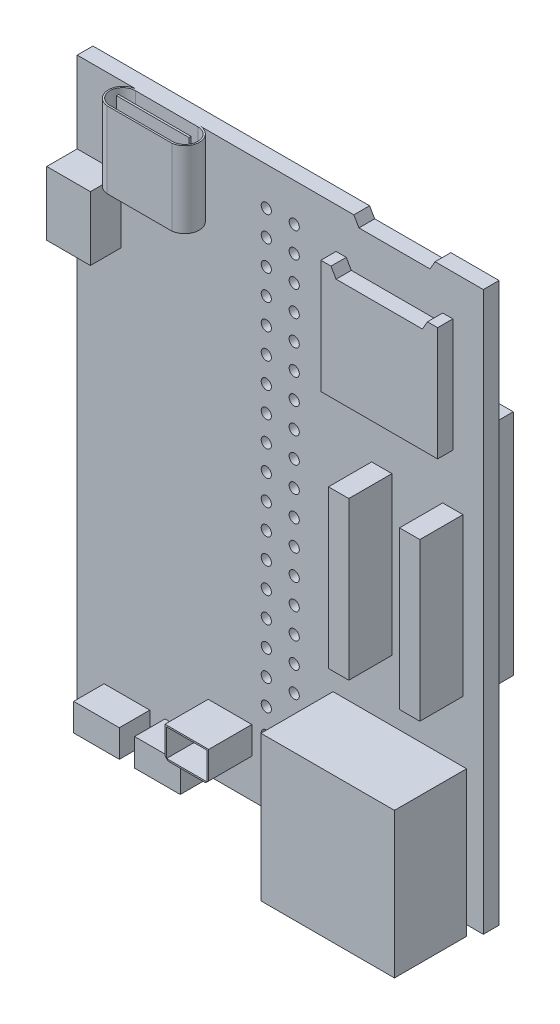
SolidWorks part; units mm, degrees
ref_plane "Front Plane" through (0, 0, 0) normal (1, 0, 0) x (0, 1, 0)
ref_plane "Top Plane" through (0, 0, 0) normal (0, 0, 1) x (0, 1, 0)
ref_plane "Right Plane" through (0, 0, 0) normal (0, 1, 0) x (-1, 0, 0)
sketch "Sketch1" plane through (0, 0, 0) normal (0, 0, 1) x (0, 1, 0)
  line L1 (-27.5, -20) -> (27.5, -20)
  line L2 (-27.5, -20) -> (-27.5, 20)
  line L3 (-27.5, 20) -> (27.5, 20)
  line L4 (27.5, -20) -> (27.5, 20)
  line L5 (-27.5, -20) -> (27.5, 20) construction
  line L6 (-27.5, 20) -> (27.5, -20) construction
  point P0 (0, 0)
  dimension "D1" = 55
  dimension "D2" = 40
extrude "Boss-Extrude1" add sketch "Sketch1" along normal blind 1.55
sketch "Sketch2" plane through (0, 0, 1.55) normal (0, 0, 1) x (1, 0, 0)
  line L0 (20, -27.5) -> (20, 27.5) construction
  line L1 (5.2, -14.2) -> (18.35, -14.2)
  line L2 (5.2, -14.2) -> (5.2, -28.5)
  line L3 (5.2, -28.5) -> (18.35, -28.5)
  line L4 (18.35, -14.2) -> (18.35, -28.5)
  line L5 (5.2, -14.2) -> (18.35, -28.5) construction
  line L6 (5.2, -28.5) -> (18.35, -14.2) construction
  line L7 (-20, -27.5) -> (20, -27.5) construction
  point P0 (11.775, -21.35)
  dimension "D1" = 1.65
  dimension "D2" = 1
  dimension "D3" = 14.3
  dimension "D4" = 13.15
extrude "Boss-Extrude2" add sketch "Sketch2" along normal blind 7.1
sketch "Sketch3" plane through (0, -28.5, 0) normal (0, -1, 0) x (1, 0, 0)
  line L0 (5.2, 8.65) -> (18.35, 8.65) construction
  line L1 (5.525, 1.85) -> (18.025, 1.85)
  line L2 (5.525, 1.85) -> (5.525, 8.35)
  line L3 (5.525, 8.35) -> (18.025, 8.35)
  line L4 (18.025, 1.85) -> (18.025, 8.35)
  line L5 (5.525, 1.85) -> (18.025, 8.35) construction
  line L6 (5.525, 8.35) -> (18.025, 1.85) construction
  line L7 (5.2, 8.65) -> (18.35, 8.65)
  line L8 (18.35, 8.65) -> (18.35, 1.55) construction
  line L9 (18.35, 8.65) -> (18.35, 1.55)
  line L10 (11.775, 8.65) -> (11.775, 2.4652) construction
  line L11 (18.35, 5.1) -> (11.2496, 5.1) construction
  line L13 (6.225, 6.85) -> (19.3448, 6.85)
  line L14 (6.225, 6.85) -> (6.225, 5.3523)
  line L15 (6.225, 5.3523) -> (19.3448, 5.3523)
  line L16 (19.3448, 6.85) -> (19.3448, 5.3523)
  line L17 (5.525, 6.1356) -> (5.2, 6.1356) construction
  line L18 (5.2, 8.65) -> (5.2, 1.55) construction
  line L19 (18.025, 6.1356) -> (18.35, 6.1356) construction
  point P0 (11.775, 5.1)
  point P12 (11.775, 5.1)
  dimension "D1" = 12.5
  dimension "D2" = 6.5
  dimension "D3" = 1.5
  dimension "D5" = 0.7
  dimension "D6" = 1.4977
extrude "Cut-Extrude1" cut sketch "Sketch3" against normal offset from surface (13.3 mm away) 1 contours L1 L4 L3 L2 L13 L16 L15 L14 region at (11.6777, -28.5, 4.8217) up to face at (11.775, -14.2, 5.1)
sketch "Sketch4" plane through (0, 0, 1.55) normal (0, 0, 1) x (1, 0, 0)
  line L0 (20, 27.5) -> (-20, 27.5) construction
  line L1 (-15.5, 27.5) -> (-6.55, 27.5)
  line L2 (-15.5, 27.5) -> (-15.5, 20)
  line L3 (-15.5, 20) -> (-6.55, 20)
  line L4 (-6.55, 27.5) -> (-6.55, 20)
  line L5 (-20, 27.5) -> (-20, -27.5) construction
  dimension "D1" = 4.5
  dimension "D2" = 7.5
  dimension "D3" = 8.95
extrude "Boss-Extrude3" add sketch "Sketch4" along normal blind 2.85
sketch "Sketch5" plane through (0, 27.5, 0) normal (0, 1, 0) x (-1, 0, 0)
  line L0 (6.55, 4.4) -> (15.5, 4.4) construction
  line L1 (6.55, 4.4) -> (15.5, 4.4) construction
  line L2 (6.55, 1.55) -> (15.5, 1.55) construction
  line L4 (11.025, 4.4) -> (11.025, 1.9427) construction
  line L7 (7.8105, 1.55) -> (6.55, 1.55)
  line L8 (6.55, 1.55) -> (6.55, 4.4)
  line L9 (6.55, 4.4) -> (7.8105, 4.4)
  line L10 (6.55, 4.4) -> (7.8105, 4.4)
  line L11 (14.2395, 4.4) -> (15.5, 4.4)
  line L12 (15.5, 4.4) -> (15.5, 2.975)
  line L13 (15.5, 2.975) -> (15.5, 1.55)
  line L14 (15.5, 1.55) -> (14.2395, 1.55)
  line L15 (7.95, 2.975) -> (14.1, 2.975) construction
  line L16 (7.95, 4.2305) -> (14.1, 4.2305)
  line L17 (7.95, 1.7195) -> (14.1, 1.7195)
  line L19 (7.45, 2.875) -> (14.6, 2.875)
  line L20 (7.45, 2.875) -> (7.45, 3.075)
  line L21 (7.45, 3.075) -> (14.6, 3.075)
  line L22 (14.6, 2.875) -> (14.6, 3.075)
  line L23 (7.45, 2.875) -> (14.6, 3.075) construction
  line L24 (7.45, 3.075) -> (14.6, 2.875) construction
  arc A0 (7.8105, 1.55) -> (7.8105, 4.4) centre (7.9857, 2.975) cw
  arc A1 (14.2395, 1.55) -> (14.2395, 4.4) centre (14.0643, 2.975) ccw
  arc A2 (7.95, 4.2305) -> (7.95, 1.7195) centre (7.95, 2.975) ccw
  arc A3 (14.1, 1.7195) -> (14.1, 4.2305) centre (14.1, 2.975) ccw
  point P17 (11.025, 2.975)
  point P22 (11.025, 2.975)
  line M7 (15.5, 1.55) -> (15.5, 4.4)
  line M8 (15.5, 4.4) -> (6.55, 4.4)
  line M9 (6.55, 4.4) -> (6.55, 1.55)
  dimension "D1" = 1.4357
  dimension "D2" = 6.15
  dimension "D3" = 1.2555
  dimension "D4" = 7.15
  dimension "D5" = 0.2
extrude "Cut-Extrude2" cut sketch "Sketch5" against normal up to surface (7.5 mm away) contours A0 M9 M8 | L7 A0 L8 | A1 L14 M7 | A1 M7 M8 region at (-15.1905, 27.5, 1.8704) region at (-15.1905, 27.5, 4.0796) region at (-6.8595, 27.5, 4.0796) region at (-6.8595, 27.5, 1.8704) up to face at (-11.025, 20, 2.975)
extrude "Cut-Extrude3" cut sketch "Sketch5<3>" against normal offset from surface (7 mm away) 0.5 contours L17 A3 L16 A2 L22 L19 L20 L21 region at (-11.025, 27.5, 4.1404) up to face at (-11.025, 20, 2.975)
sketch "Sketch5<3>" plane through (0, 27.5, 0) normal (0, 1, 0) x (-1, 0, 0) same geometry as "Sketch5"
sketch "Sketch6" plane through (0, 0, 1.55) normal (0, 0, 1) x (1, 0, 0)
  line L0 (16, 23.5) -> (15.5, 22.634)
  line L1 (17, 12.3) -> (5.5, 12.3)
  line L2 (17, 12.3) -> (17, 23.5)
  line L3 (17, 23.5) -> (16, 23.5)
  line L4 (5.5, 12.3) -> (5.5, 23.5)
  line L5 (18.35, -28.5) -> (18.35, -14.2) construction
  line L6 (18.35, -28.5) -> (18.35, -14.2) construction
  line L7 (15.5, 22.634) -> (7, 22.634)
  line L8 (7, 22.634) -> (6.5, 23.5)
  line L9 (6.5, 23.5) -> (5.5, 23.5)
  line L10 (20, 27.5) -> (-7.8105, 27.5) construction
  line L12 (20, -27.5) -> (20, 27.5) construction
  dimension "D1" = 120
  dimension "D2" = 8.5
  dimension "D3" = 3
  dimension "D4" = 1
  dimension "D5" = 11.5
  dimension "D6" = 11.2
  dimension "D7" = 4
extrude "Boss-Extrude4" add sketch "Sketch6" along normal blind 1.5
sketch "Sketch7" plane through (0, 0, 1.55) normal (0, 0, 1) x (1, 0, 0)
  line L3 (16, 23.5) -> (15.5, 22.634) construction
  line L5 (7, 22.634) -> (6.5, 23.5) construction
  line L6 (15.5, 22.634) -> (7, 22.634) construction
  line L7 (16, 23.5) -> (15.5, 22.634) construction
  line L8 (7, 22.634) -> (6.5, 23.5) construction
  line L9 (15.5, 22.634) -> (7, 22.634) construction
  line L10 (7.25, 27.5) -> (7.75, 26.634)
  line L11 (20, 27.5) -> (-7.8105, 27.5) construction
  line L12 (15.25, 27.5) -> (14.75, 26.634)
  line L13 (7.75, 26.634) -> (14.75, 26.634)
  line L14 (7.25, 27.5) -> (15.25, 27.5)
  point P10 (11.25, 26.634)
  point P11 (11.25, 22.634)
  dimension "D1" = 7
  dimension "D2" = 120
extrude "Cut-Extrude4" cut sketch "Sketch7" against normal blind 10
sketch "Sketch8" plane through (0, 0, 1.55) normal (0, 0, 1) x (1, 0, 0)
  line L0 (-20, -27.5) -> (5.2, -27.5) construction
  line L1 (-17.35, -27.5) -> (-12.85, -27.5)
  line L2 (-17.35, -27.5) -> (-17.35, -24.8)
  line L3 (-17.35, -24.8) -> (-12.85, -24.8)
  line L4 (-12.85, -27.5) -> (-12.85, -24.8)
  line L5 (-20, 27.5) -> (-20, -27.5) construction
  line L6 (-12.1, -27.5) -> (-12.1, -22.0575) construction
  line L7 (-6.85, -24.8) -> (-11.35, -24.8)
  line L8 (-11.35, -27.5) -> (-11.35, -24.8)
  line L9 (-6.85, -27.5) -> (-11.35, -27.5)
  line L10 (-6.85, -27.5) -> (-6.85, -24.8)
  line L12 (-7.1, -21) -> (-2.8, -21)
  line L13 (-7.1, -21) -> (-7.1, -24)
  line L14 (-7.1, -24) -> (-2.8, -24)
  line L15 (-2.8, -21) -> (-2.8, -24)
  line M20 (-20, -27.5) -> (5.2, -27.5)
  dimension "D1" = 4.5
  dimension "D2" = 2.7
  dimension "D3" = 13.15
  dimension "D4" = 1.5
  dimension "D5" = 12.9
  dimension "D6" = 3.5
  dimension "D7" = 3
  dimension "D8" = 4.3
extrude "Boss-Extrude5" add sketch "Sketch8" along normal blind 3 contours L10 L7 L8 M20 | L4 L3 L2 M20 region at (-15.1, -26.15, 1.55) region at (-9.1, -26.15, 1.55)
sketch "Sketch9" plane through (0, -27.5, 0) normal (0, -1, 0) x (1, 0, 0)
  line L0 (-12.1, 3.8788) -> (-12.1, 2.2212) construction
  line L1 (-11.35, 4.55) -> (-11.35, 1.55) construction
  line L2 (-12.85, 4.55) -> (-12.85, 1.55) construction
  line L3 (-17.35, 4.55) -> (-17.35, 1.55) construction
  line L5 (-12.1, 3.05) -> (-12.85, 3.05) construction
  line L6 (-11.35, 4.55) -> (-11.35, 1.55) construction
  line L7 (-12.85, 4.55) -> (-12.85, 1.55) construction
  line L8 (-17.35, 4.55) -> (-17.35, 1.55) construction
  line L9 (-17.35, 4.55) -> (-12.85, 4.55) construction
  line L10 (-12.1, 3.05) -> (-11.35, 3.05) construction
  line L11 (-17.35, 4.55) -> (-12.85, 4.55) construction
  line L13 (-15.1, 4.55) -> (-15.1, 1.55) construction
  circle A0 centre (-15.1, 3.05) radius 1
  circle A1 centre (-9.1, 3.05) radius 1
  point P10 (-12.85, 3.05)
  point P18 (-17.1, 4.55)
  point P21 (0, 0)
  point P22 (0, 0)
  dimension "D1" = 2
extrude "Boss-Extrude6" add sketch "Sketch9" along normal blind 0.5 contours A1 | A0 region at (-9.1, -27.5, 3.05)
sketch "Sketch10" plane through (0, 0, 1.55) normal (0, 0, 1) x (1, 0, 0)
  line L0 (17, 12.3) -> (17, 23.5) construction
  line L1 (17, 12.3) -> (17, 23.5) construction
  line L2 (18.35, -14.2) -> (5.2, -14.2) construction
  line L3 (18, 7.3) -> (16, 7.3)
  line L4 (18, 7.3) -> (18, -8.2)
  line L5 (18, -8.2) -> (16, -8.2)
  line L6 (16, 7.3) -> (16, -8.2)
  line L8 (13.5, 8.7091) -> (13.5, -10.2301) construction
  line L9 (9, -8.2) -> (11, -8.2)
  line L10 (11, 7.3) -> (11, -8.2)
  line L11 (9, 7.3) -> (11, 7.3)
  line L12 (9, 7.3) -> (9, -8.2)
  line L13 (20, -27.5) -> (20, 27.5) construction
  dimension "D1" = 15.5
  dimension "D2" = 2
  dimension "D3" = 6
  dimension "D4" = 5
  dimension "D5" = 2
extrude "Boss-Extrude7" add sketch "Sketch10" along normal blind 4.25
extrude "Boss-Extrude9" add sketch "Sketch8<4>" along normal blind 4.25 separate body contours L15 L12 L13 L14 region at (-4.95, -22.5, 1.55)
sketch "Sketch8<4>" plane through (0, 0, 1.55) normal (0, 0, 1) x (1, 0, 0) same geometry as "Sketch8"
shell "Shell2" thickness 0.15 removed face at (-4.95, -22.5, 5.8)
combine bodies "Combine1" operation type add bodies to combine 111 113
chamfer "Chamfer1" distance 0.3 angle 45 2 edges at (-7.1, -24, 3.675) (-2.8, -24, 3.675) tangent propagation no
sketch "Sketch11" plane through (0, 0, 1.55) normal (0, 0, 1) x (1, 0, 0)
  line L0 (7.25, 27.5) -> (-7.8105, 27.5) construction
  line L1 (2.75, -25.5) -> (-2.75, -25.5) construction
  line L2 (2.75, -25.5) -> (2.75, 25.5) construction
  line L3 (2.75, 25.5) -> (-2.75, 25.5) construction
  line L4 (-2.75, -25.5) -> (-2.75, 25.5) construction
  line L5 (-6.85, -27.5) -> (5.2, -27.5) construction
  line L6 (-14.2395, 27.5) -> (-20, 27.5) construction
  line L10 (2.75, 0) -> (20, 0) construction
  line L11 (20, -27.5) -> (20, 27.5) construction
  line L12 (-2.75, 0) -> (-20, 0) construction
  line L13 (-20, 27.5) -> (-20, -27.5) construction
  line L16 (0, 25.5) -> (0, -25.5) construction
  line L17 (0, 23.75) -> (1.375, 23.75) construction
  line L18 (1.375, 23.75) -> (2.75, 23.75) construction
  line L19 (1.375, 23.75) -> (1.375, 25.5) construction
  line L20 (1.375, -23.75) -> (1.375, -25.5) construction
  circle A0 centre (1.375, 23.75) radius 0.5
  circle A1 centre (1.375, 21.25) radius 0.5
  circle A2 centre (1.375, 18.75) radius 0.5
  circle A3 centre (1.375, 16.25) radius 0.5
  circle A4 centre (1.375, 13.75) radius 0.5
  circle A5 centre (1.375, 11.25) radius 0.5
  circle A6 centre (1.375, 8.75) radius 0.5
  circle A7 centre (1.375, 6.25) radius 0.5
  circle A8 centre (1.375, 3.75) radius 0.5
  circle A9 centre (1.375, 1.25) radius 0.5
  circle A10 centre (1.375, -1.25) radius 0.5
  circle A11 centre (1.375, -3.75) radius 0.5
  circle A12 centre (1.375, -6.25) radius 0.5
  circle A13 centre (1.375, -8.75) radius 0.5
  circle A14 centre (1.375, -11.25) radius 0.5
  circle A15 centre (1.375, -13.75) radius 0.5
  circle A16 centre (1.375, -16.25) radius 0.5
  circle A17 centre (1.375, -18.75) radius 0.5
  circle A18 centre (1.375, -21.25) radius 0.5
  circle A19 centre (1.375, -23.75) radius 0.5
  circle A20 centre (-1.375, -23.75) radius 0.5
  circle A21 centre (-1.375, -21.25) radius 0.5
  circle A22 centre (-1.375, -18.75) radius 0.5
  circle A23 centre (-1.375, -16.25) radius 0.5
  circle A24 centre (-1.375, -13.75) radius 0.5
  circle A25 centre (-1.375, -11.25) radius 0.5
  circle A26 centre (-1.375, -8.75) radius 0.5
  circle A27 centre (-1.375, -6.25) radius 0.5
  circle A28 centre (-1.375, -3.75) radius 0.5
  circle A29 centre (-1.375, -1.25) radius 0.5
  circle A30 centre (-1.375, 1.25) radius 0.5
  circle A31 centre (-1.375, 3.75) radius 0.5
  circle A32 centre (-1.375, 6.25) radius 0.5
  circle A33 centre (-1.375, 8.75) radius 0.5
  circle A34 centre (-1.375, 11.25) radius 0.5
  circle A35 centre (-1.375, 13.75) radius 0.5
  circle A36 centre (-1.375, 16.25) radius 0.5
  circle A37 centre (-1.375, 18.75) radius 0.5
  circle A38 centre (-1.375, 23.75) radius 0.5
  circle A39 centre (-1.375, 21.25) radius 0.5
  point P21 (0, 0)
  point P105 (-17.1197, 27.5)
  dimension "D5" = 1
  dimension "D1" = 5.5
  dimension "D2" = 2
  dimension "D3" = 2
  dimension "D4" = 51
  dimension "D6" = 20
  dimension "D7" = 2.5
  dimension "D8" = 27.5
extrude "Cut-Extrude5" cut sketch "Sketch11" against normal up to next (1.55 mm away)
sketch "Sketch12" plane through (0, 0, 1.55) normal (0, 0, 1) x (1, 0, 0)
  line L0 (-20, 27.5) -> (-20, -27.5) construction
  line L1 (-20, 19.5) -> (-15.7, 19.5)
  line L2 (-20, 19.5) -> (-20, 13.2)
  line L3 (-20, 13.2) -> (-15.7, 13.2)
  line L4 (-15.7, 19.5) -> (-15.7, 13.2)
  line L5 (-14.2395, 27.5) -> (-20, 27.5) construction
  dimension "D1" = 6.3
  dimension "D2" = 4.3
  dimension "D3" = 8
extrude "Boss-Extrude10" add sketch "Sketch12" along normal blind 3 separate body
shell "Shell3" thickness 0.2 removed face at (-20, 16.35, 3.05)
sketch "Sketch13" plane through (0, 0, 0) normal (0, 0, -1) x (1, 0, 0)
  line L1 (15.5, 8.5) -> (18.4, 8.5)
  line L2 (15.5, 8.5) -> (15.5, -14)
  line L3 (15.5, -14) -> (18.4, -14)
  line L4 (18.4, 8.5) -> (18.4, -14)
  line L6 (-20, -27.5) -> (-20, 27.5) construction
  line L8 (0, 0) -> (0, -6.8775) construction
  line L9 (-15.5, -14) -> (-18.4, -14)
  line L10 (-18.4, 8.5) -> (-18.4, -14)
  line L11 (-15.5, 8.5) -> (-18.4, 8.5)
  line L12 (-15.5, 8.5) -> (-15.5, -14)
  dimension "D1" = 13.5
  dimension "D2" = 2.9
  dimension "D3" = 22.5
  dimension "D4" = 35.5
extrude "Boss-Extrude11" add sketch "Sketch13" along normal blind 3
